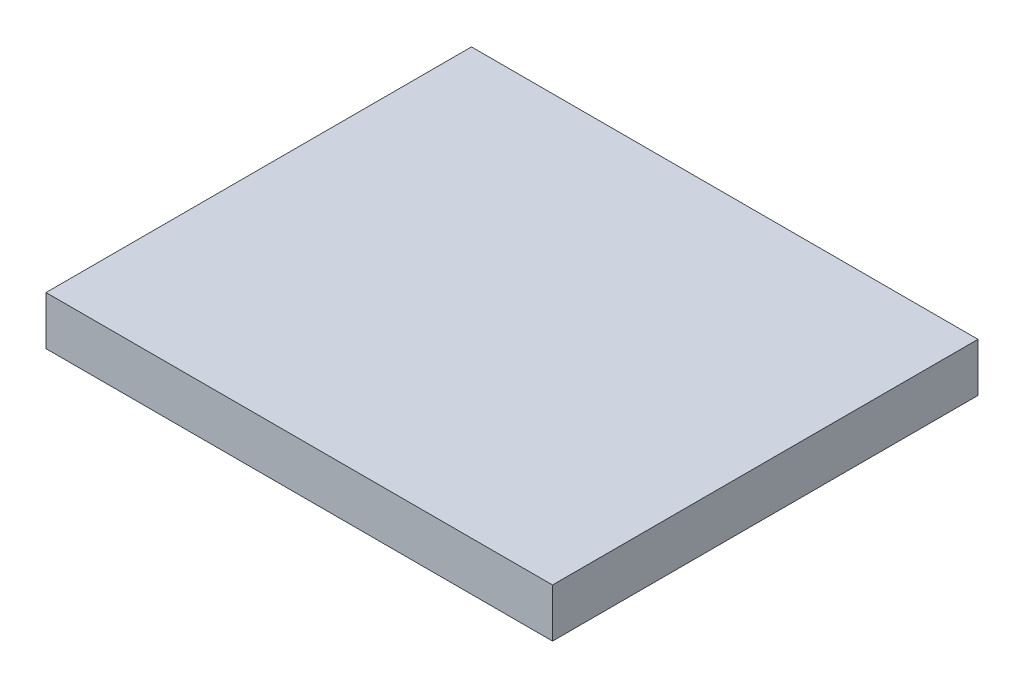
SolidWorks part; units mm, degrees
ref_plane "Front" through (0, 0, 0) normal (0, 0, 1) x (1, 0, 0)
ref_plane "Top" through (0, 0, 0) normal (0, 1, 0) x (1, 0, 0)
ref_plane "Right" through (0, 0, 0) normal (1, 0, 0) x (0, 0, -1)
sketch "Sketch1" plane through (0, 0, 0) normal (0, 1, 0) x (1, 0, 0)
  line L1 (-62.5, -52.5) -> (62.5, -52.5)
  line L2 (-62.5, -52.5) -> (-62.5, 52.5)
  line L3 (-62.5, 52.5) -> (62.5, 52.5)
  line L4 (62.5, -52.5) -> (62.5, 52.5)
  line L5 (-62.5, -52.5) -> (62.5, 52.5) construction
  line L6 (-62.5, 52.5) -> (62.5, -52.5) construction
  point P0 (0, 0)
  dimension "D1" = 125
  dimension "D2" = 105
extrude "Test_Base_Postion" add sketch "Sketch1" along normal blind 12
sketch "Front_Fingers_Position" plane through (0, 12, 0) normal (0, 1, 0) x (1, 0, 0)
  line L0 (-62.5, 52.5) -> (-62.5, -52.5) construction
  line L1 (-58.5, 42) -> (-3.5, 42)
  line L2 (-58.5, 42) -> (-58.5, 10)
  line L3 (-58.5, 10) -> (-3.5, 10)
  line L4 (-3.5, 42) -> (-3.5, 10)
  line L5 (-3.5, 10) -> (-3.5, -10) construction
  line L6 (-58.5, -10) -> (-3.5, -10)
  line L7 (-58.5, -10) -> (-58.5, -42)
  line L8 (-58.5, -42) -> (-3.5, -42)
  line L9 (-3.5, -10) -> (-3.5, -42)
  line L10 (0, 0) -> (-3.5, 0) construction
  line L11 (-62.5, -52.5) -> (62.5, -52.5) construction
  line L12 (-58.5, 26) -> (-3.5, 26) construction
  line L13 (-31, 42) -> (-31, 10) construction
  line L14 (-31, -10) -> (-31, -42) construction
  line L15 (-58.5, -26) -> (-3.5, -26) construction
  dimension "D1" = 32
  dimension "D2" = 55
  dimension "D3" = 32
  dimension "D4" = 55
  dimension "D5" = 20
  dimension "D6" = 4
sketch "Drive_Gear_Motor_Position" plane through (0, 12, 0) normal (0, 1, 0) x (1, 0, 0)
  line L0 (-46.5, 35) -> (-46.5, 26) construction
  line L1 (-58.5, 35) -> (-34.5, 35)
  line L2 (-58.5, 35) -> (-58.5, -1)
  line L3 (-58.5, -1) -> (-34.5, -1)
  line L4 (-34.5, 35) -> (-34.5, -1)
  line L5 (-46.5, -1) -> (-46.5, 8) construction
  line L6 (-58.5, 26) -> (-3.5, 26) construction
  line L7 (-55.5, 26) -> (-37.5, 26) construction
  line L9 (-62.5, 52.5) -> (-62.5, -52.5) construction
  circle A0 centre (-46.5, 26) radius 9
  circle A1 centre (-46.5, 8) radius 9 construction
  circle A2 centre (-46.5, 26) radius 14.875
  dimension "D5" = 29.75
  dimension "D6" = 16
  dimension "D1" = 36
  dimension "D2" = 24
  dimension "D3" = 9
  dimension "D4" = 9
sketch "Thumb_Position" plane through (0, 12, 0) normal (0, 1, 0) x (1, 0, 0)
  line L0 (62.5, -52.5) -> (62.5, 52.5) construction
  line L1 (53.5, -12) -> (21.5, -12)
  line L2 (53.5, -12) -> (53.5, 43)
  line L3 (53.5, 43) -> (21.5, 43)
  line L4 (21.5, -12) -> (21.5, 43)
  line L5 (37.5, 43) -> (37.5, -12) construction
  line L6 (55.5, -12) -> (19.5, -12)
  line L7 (55.5, -12) -> (55.5, 12)
  line L8 (55.5, 12) -> (19.5, 12)
  line L9 (19.5, -12) -> (19.5, 12)
  line L10 (37.5, 12) -> (37.5, -12) construction
  line L12 (55.5, 0) -> (19.5, 0) construction
  circle A1 centre (46.5, 0) radius 9
  circle A2 centre (46.5, 0) radius 14.875
  dimension "D6" = 18
  dimension "D7" = 16
  dimension "D5" = 29.75
  dimension "D1" = 55
  dimension "D2" = 32
  dimension "D3" = 36
  dimension "D4" = 24
sketch "Gears_Position" plane through (0, 0, 0) normal (0, -1, 0) x (1, 0, 0)
  line L0 (-58.5, 26) -> (-46.5, 26) construction
  line L2 (0, 0) -> (-62.5, 0) construction
  line L3 (-62.5, -52.5) -> (-62.5, 52.5) construction
  circle A0 centre (-46.5, 26) radius 14.875
  circle A1 centre (-18.9084, 14.875) radius 14.875
  circle A2 centre (-18.9084, -14.875) radius 14.875
  circle A3 centre (-46.5, -26) radius 14.875 construction
  dimension "D2" = 29.75
  dimension "D3" = 29.75
  dimension "D1" = 12
